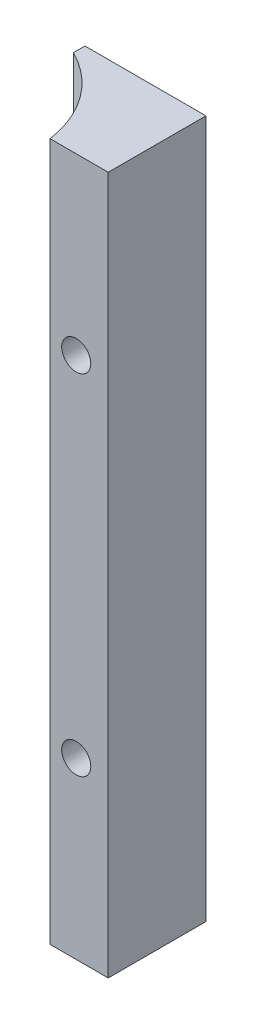
SolidWorks part; units mm, degrees
ref_plane "Front" through (0, 0, 0) normal (0, 0, 1) x (1, 0, 0)
ref_plane "Top" through (0, 0, 0) normal (0, 1, 0) x (1, 0, 0)
ref_plane "Right" through (0, 0, 0) normal (1, 0, 0) x (0, 0, -1)
sketch "Sketch1" plane through (0, 0, 0) normal (0, 1, 0) x (1, 0, 0)
  line L0 (0, 0) -> (0, 8.4)
  line L1 (0, 8.4) -> (-10.4025, 8.4)
  line L2 (-10.4025, 8.4) -> (-10.4025, 7.4)
  line L3 (-5, 0) -> (0, 0)
  arc A0 (-10.4025, 7.4) -> (-5, 0) centre (-14.7211, -1.425) cw
  dimension "D3" = 9.825
  dimension "D1" = 5
  dimension "D2" = 8.4
  dimension "D4" = 1.425
  dimension "D5" = 1
extrude "Boss-Extrude1" add sketch "Sketch1" along normal blind 60
sketch "Sketch2" plane through (0, 0, 0) normal (0, 0, 1) x (1, 0, 0)
  line L0 (-2.75, 60) -> (-2.75, 0) construction
  line L1 (-5, 60) -> (0, 60) construction
  line L2 (-5, 0) -> (0, 0) construction
  line L3 (-5, 60) -> (-5, 0) construction
  point P6 (-2.75, 45)
  point P7 (-2.75, 15)
  dimension "D1" = 15
  dimension "D2" = 15
  dimension "D3" = 2.25
hole_wizard "Ø2.5mm Dowel Hole1" positions "3DSketch1" profile "Sketch3" hole size "Ø2.5" standard "ANSI Metric" end condition up to next
sketch3d "3DSketch1"
  point P0 (-2.75, 45, 0)
  point P3 (-2.75, 15, 0)
sketch "Sketch3" plane through (-2.75, 45, 0) normal (1, 0, 0) x (0, -1, 0)
  line L0 (0, 0) -> (0, 8.4)
  line L1 (0, 8.4) -> (1.25, 8.4)
  line L2 (1.25, 8.4) -> (1.25, 0)
  line L5 (1.25, 0) -> (0, 0)
  line L11 (0, -6.35) -> (0, 107.95) construction
  dimension "Thru Hole Dia." = 2.5
  dimension "Thru Hole Depth" = 8.4
